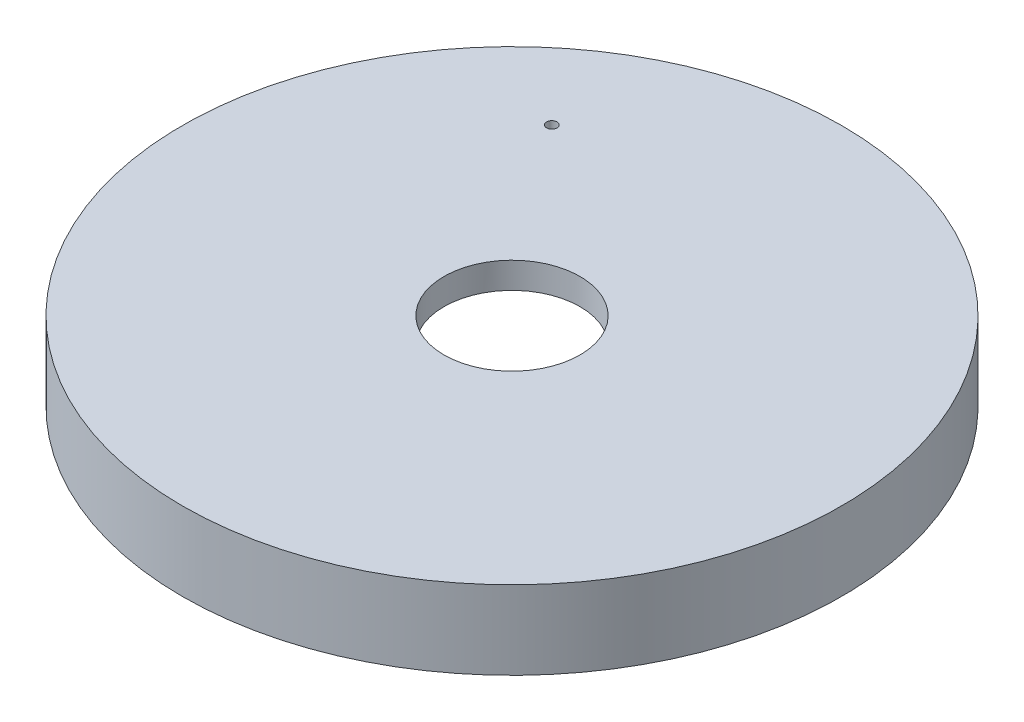
SolidWorks part; units mm, degrees
material "HYPALON"
ref_plane "Płaszczyzna przednia" through (0, 0, 0) normal (0, 0, 1) x (1, 0, 0)
ref_plane "Płaszczyzna górna" through (0, 0, 0) normal (0, 1, 0) x (1, 0, 0)
ref_plane "Płaszczyzna prawa" through (0, 0, 0) normal (1, 0, 0) x (0, 0, -1)
sketch "Szkic1" plane through (0, 0, 0) normal (0, 0, 1) x (1, 0, 0)
  line L0 (13, 2.5) -> (63, 2.5)
  line L1 (63, 2.5) -> (63, -12.5)
  line L2 (63, -12.5) -> (40.4748, -12.5)
  line L3 (40.4748, -12.5) -> (13, -2.5)
  line L4 (13, -2.5) -> (13, 2.5)
  line L5 (0, 24.6083) -> (0, -34.5814) construction
  point P8 (13, 0)
  dimension "D1" = 13
  dimension "D2" = 63
  dimension "D3" = 160
  dimension "D4" = 5
  dimension "D5" = 15
revolve "Obrót1" add sketch "Szkic1" angle 360 about L5
sketch "Szkic2" plane through (0, 0, 0) normal (0, 1, 0) x (1, 0, 0)
  line L0 (-27.786, 35.3969) -> (0, 0) construction
  line L1 (0, 0) -> (33.1748, -42.2618) construction
  circle A0 centre (-27.786, 35.3969) radius 1
  dimension "D1" = 45
  dimension "D2" = 2
extrude "Wytnij-wyciągnięcie2" cut sketch "Szkic2" against normal mid plane 30
